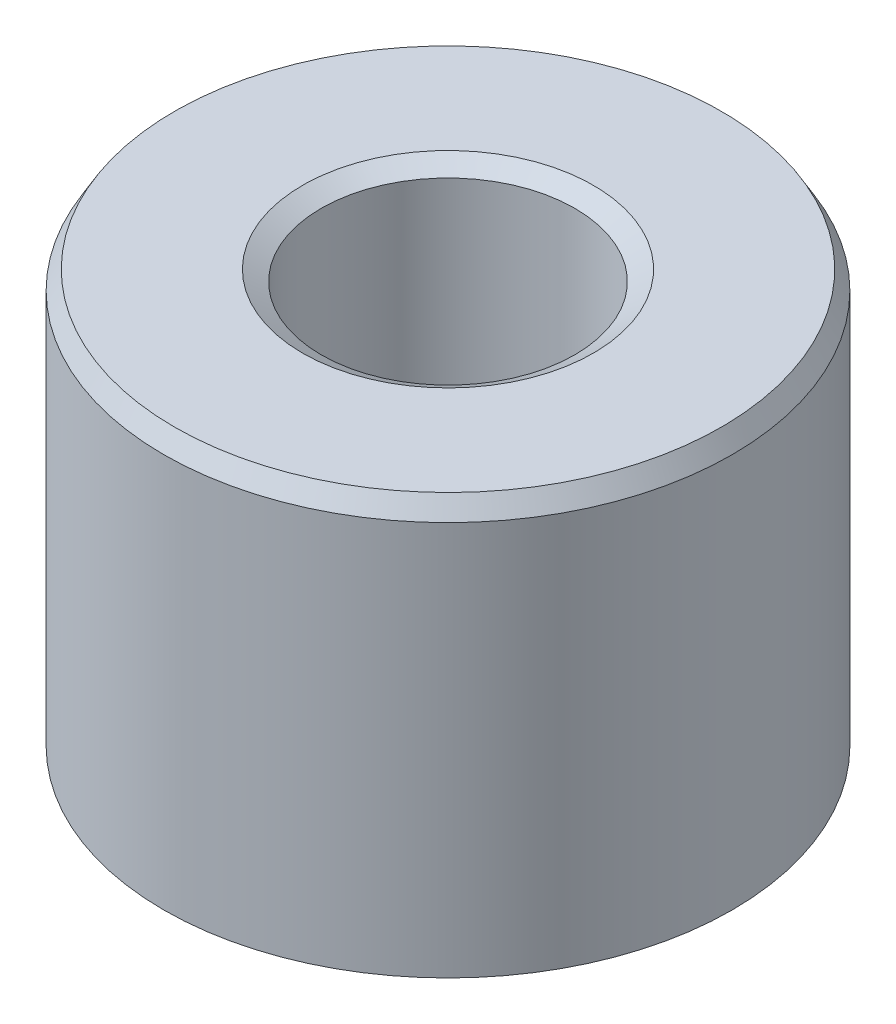
SolidWorks part; units mm, degrees
ref_plane "Front Plane" through (0, 0, 0) normal (0, 0, 1) x (1, 0, 0)
ref_plane "Top Plane" through (0, 0, 0) normal (0, 1, 0) x (1, 0, 0)
ref_plane "Right Plane" through (0, 0, 0) normal (1, 0, 0) x (0, 0, -1)
sketch "Sketch1" plane through (0, 0, 0) normal (0, 1, 0) x (1, 0, 0)
  circle A0 centre (0, 0) radius 50
  dimension "SLEEVE_OD" = 100
extrude "Boss-Extrude1" add sketch "Sketch1" along normal blind 74.5254
sketch "Sketch2" plane through (0, 0, 0) normal (0, 1, 0) x (1, 0, 0)
  circle A0 centre (0, 0) radius 22.3222
  dimension "BORE_D" = 44.6444
extrude "Cut-Extrude1" cut sketch "Sketch2" along normal through all
chamfer "Chamfer1" distance 3.2609 angle 30 4 edges at (0, 74.5254, 22.3222) (0, 0, 22.3222) (0, 0, 50) (0, 74.5254, 50) first distance on face at (0, 74.5254, 22.3222) first distance on face at (0, 0, 22.3222) first distance on face at (0, 74.5254, 50)
